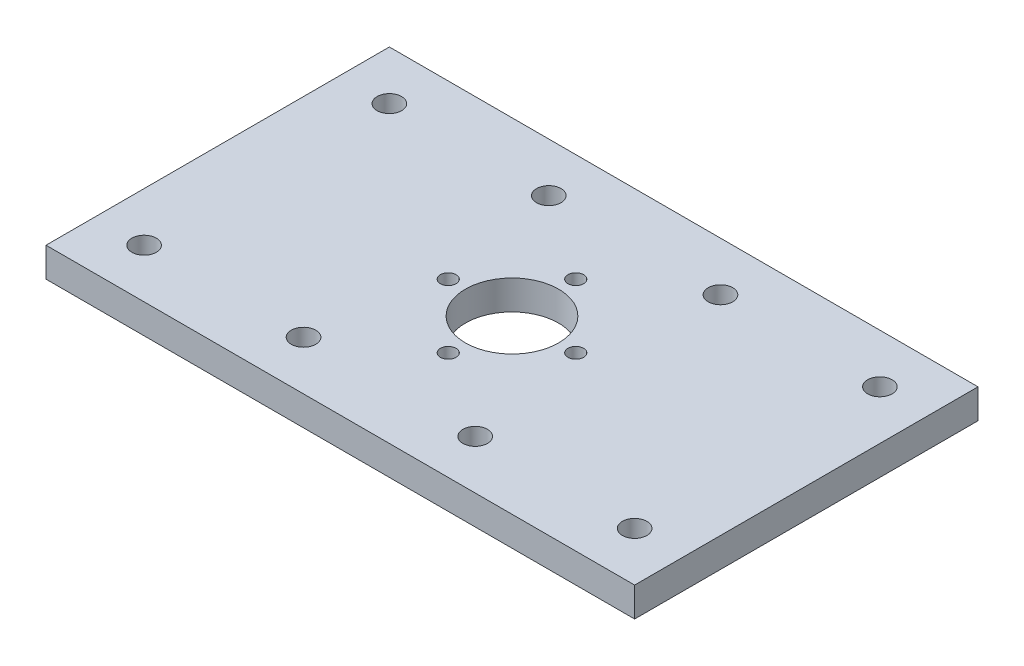
SolidWorks part; units mm, degrees
ref_plane "Front Plane" through (0, 0, 0) normal (0, 0, 1) x (1, 0, 0)
ref_plane "Top Plane" through (0, 0, 0) normal (0, 1, 0) x (1, 0, 0)
ref_plane "Right Plane" through (0, 0, 0) normal (1, 0, 0) x (0, 0, -1)
sketch "Sketch1" plane through (0, 0, 0) normal (0, 1, 0) x (1, 0, 0)
  line L0 (0, -55) -> (0, 55) construction
  line L1 (-60, 35) -> (60, 35)
  line L2 (-60, 35) -> (-60, -35)
  line L3 (-60, -35) -> (60, -35)
  line L4 (60, 35) -> (60, -35)
  line L5 (-60, 35) -> (60, -35) construction
  line L6 (-60, -35) -> (60, 35) construction
  line L7 (-55, 0) -> (55, 0) construction
  circle A0 centre (0, 0) radius 13 construction
  circle A1 centre (0, 13) radius 1.5 construction
  circle A2 centre (13, 0) radius 1.5 construction
  circle A3 centre (0, -13) radius 1.5 construction
  circle A4 centre (-13, 0) radius 1.5 construction
  circle A7 centre (0, 0) radius 9.5
  circle A8 centre (-17.5, 25) radius 2.5
  circle A9 centre (17.5, 25) radius 2.5
  circle A10 centre (17.5, -25) radius 2.5
  circle A11 centre (-17.5, -25) radius 2.5
  circle A12 centre (-50, 25) radius 2.5
  circle A13 centre (-50, -25) radius 2.5
  circle A14 centre (50, -25) radius 2.5
  circle A15 centre (50, 25) radius 2.5
  dimension "D1" = 26
  dimension "D2" = 3
  dimension "D4" = 19
  dimension "D7" = 5
  dimension "D10" = 5
  dimension "D5" = 17.5
  dimension "D6" = 120
  dimension "D8" = 70
  dimension "D9" = 25
  dimension "D11" = 50
  dimension "D12" = 25
  dimension "D3" = 4
extrude "Boss-Extrude1" add sketch "Sketch1" along normal blind 6
hole_wizard "CSK for M3 Flat Head Machine Screw1" positions "Sketch7" profile "Sketch8" countersink size "M3" standard "ANSI Metric" end condition through all
sketch "Sketch7" plane through (0, 0, 0) normal (0, -1, 0) x (-1, 0, 0)
  point P0 (-13, 0)
  point P3 (0, -13)
  point P6 (13, 0)
  point P9 (0, 13)
sketch "Sketch8" plane through (13, 0, 0) normal (1, 0, 0) x (0, 0, -1)
  line L0 (0, 0) -> (0, 6)
  line L1 (0, 6) -> (1.6, 6)
  line L2 (1.6, 6) -> (1.6, 1.55)
  line L3 (1.6, 1.55) -> (3.15, 0)
  line L5 (3.15, 0) -> (0, 0)
  line L6 (-1.6, 1.55) -> (-3.15, 0) construction
  line L11 (0, -6.35) -> (0, 107.95) construction
  dimension "Thru Hole Dia." = 3.2
  dimension "Thru Hole Depth" = 6
  dimension "Near C'Sink Dia." = 6.3
  dimension "Near C'Sink Angle" = 90
sketch "Sketch9" plane through (0, 0, 0) normal (0, 1, 0) x (1, 0, 0)
  line L0 (0, -55) -> (0, 55) construction
  line L1 (-55, 0) -> (55, 0) construction
  circle A0 centre (17.5, 25) radius 6
  circle A1 centre (-17.5, 25) radius 6
  circle A2 centre (-17.5, -25) radius 6
  circle A3 centre (17.5, -25) radius 6
  dimension "D1" = 12
equation "\"testbed_height\" = 91.50mm"
equation "\"plate_thickness\" = 6mm"
equation "\"main_body_splay_length\" = 48.5mm"
equation "\"splay_shaft_length_no_wires\" = 10mm"
equation "\"splay_shaft_length_wires\" = 6.5mm"
equation "\"timing_pulley_offset\" = 0mm"
equation "\"effective_motor_length\" = \"timing_pulley_offset\" + \"splay_shaft_length_no_wires\" + \"main_body_splay_length\""
equation "\"80_20_side\" = 25.4mm"
equation "\"80_20_length\" = 152.4mm"
equation "\"80_20_optic_mount_length\" = \"80_20_length\" - 25.4mm"
equation "\"optic_board_hole_size\" = 6.35mm"
equation "\"total_mounting_length\" = \"testbed_height\" - \"effective_motor_length\" - \"80_20_side\""
equation "\"mounting_vertical_portion_height\" = \"total_mounting_length\" - 2 * \"plate_thickness\""
equation "\"face_mount_width\" = 15.25mm"
equation "\"center_dist_to_face_mount_vertical_screws\" = 5mm"
equation "\"D1@Boss-Extrude1\"=\"plate_thickness\""
